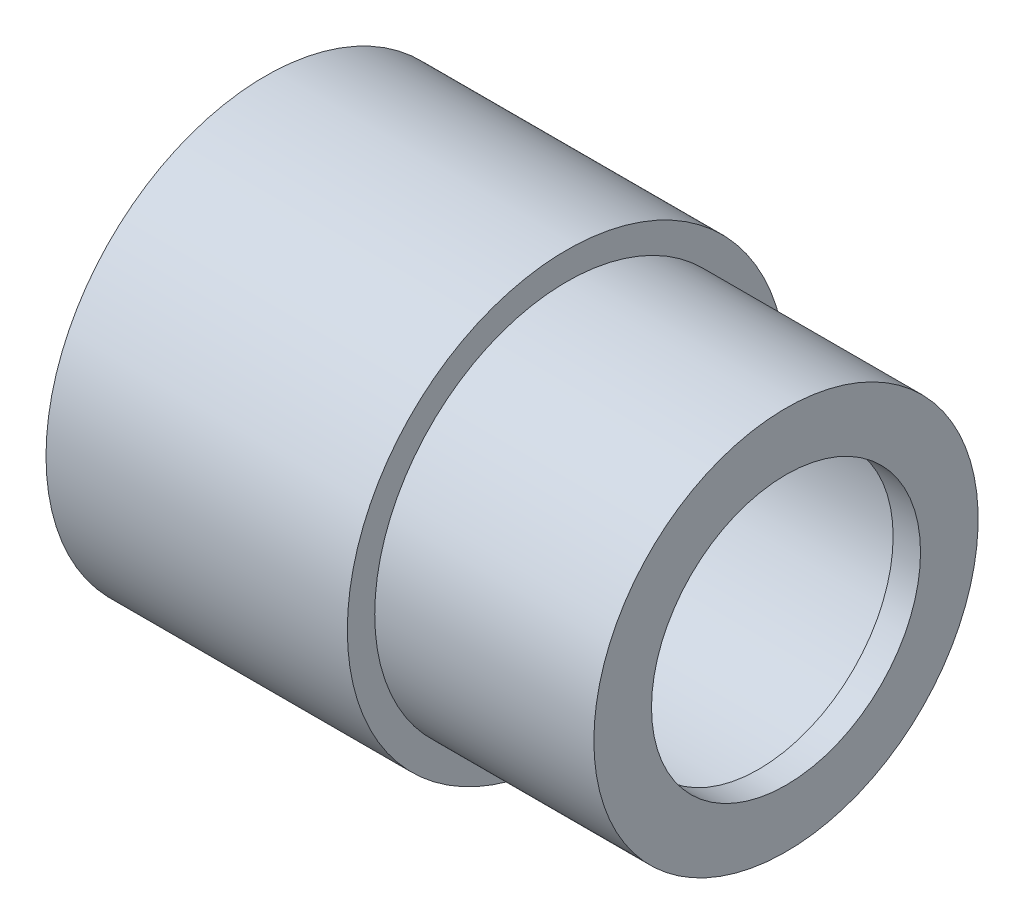
SolidWorks part; units mm, degrees
ref_plane "Front Plane" through (0, 0, 0) normal (0, 0, 1) x (1, 0, 0)
ref_plane "Top Plane" through (0, 0, 0) normal (0, 1, 0) x (1, 0, 0)
ref_plane "Right Plane" through (0, 0, 0) normal (1, 0, 0) x (0, 0, -1)
sketch "Sketch1" plane through (0, 0, 0) normal (0, 0, 1) x (1, 0, 0)
  line L0 (0, 0) -> (0, 76.2) construction
  line L1 (0, 0) -> (248.6575, 0) construction
  line L2 (0, 89.0805) -> (0, 101.7805)
  line L3 (0, 101.7805) -> (139.7, 101.7805)
  line L4 (139.7, 101.7805) -> (139.7, 89.0805)
  line L5 (139.7, 89.0805) -> (241.3, 89.0805)
  line L6 (241.3, 89.0805) -> (241.3, 62.3614)
  line L7 (0, 89.0805) -> (127, 89.0805)
  line L8 (127, 89.0805) -> (127, 76.3805)
  line L9 (127, 76.3805) -> (228.6, 76.3805)
  line L10 (228.6, 76.3805) -> (228.6, 62.3614)
  line L11 (228.6, 62.3614) -> (241.3, 62.3614)
  line L12 (127, 89.0805) -> (139.7, 89.0805) construction
  dimension "D1" = 76.2
  dimension "D2" = 127
  dimension "D3" = 12.7
  dimension "D4" = 101.6
revolve "Revolve1" add sketch "Sketch1" angle 360 about L1
sketch "Sketch7" plane through (0, 0, 0) normal (-1, 0, 0) x (0, 0, 1)
  circle A0 centre (0, 0) radius 101.7805
curve "Helix/Spiral1" pitch 3.175 height 31.75 turns 10
